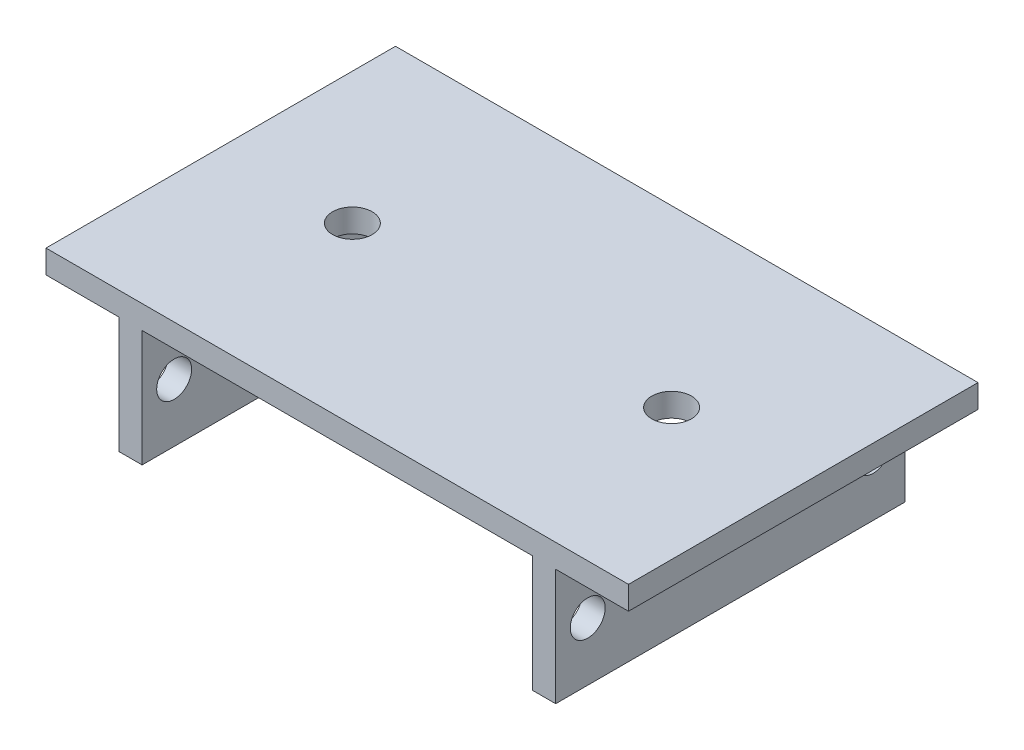
SolidWorks part; units mm, degrees
ref_plane "Front Plane" through (0, 0, 0) normal (0, 0, 1) x (1, 0, 0)
ref_plane "Top Plane" through (0, 0, 0) normal (0, 1, 0) x (1, 0, 0)
ref_plane "Right Plane" through (0, 0, 0) normal (1, 0, 0) x (0, 0, -1)
sketch "Sketch1" plane through (0, 0, 0) normal (0, 1, 0) x (1, 0, 0)
  line L1 (-72.1861, 30.4945) -> (-22.1861, 30.4945)
  line L2 (-72.1861, 30.4945) -> (-72.1861, 0.4945)
  line L3 (-72.1861, 0.4945) -> (-22.1861, 0.4945)
  line L4 (-22.1861, 30.4945) -> (-22.1861, 0.4945)
  dimension "D1" = 50
  dimension "D2" = 30
extrude "Boss-Extrude1" add sketch "Sketch1" along normal blind 2
sketch "Sketch6" plane through (0, 0, 0) normal (0, 1, 0) x (1, 0, 0)
  line L0 (-72.1861, 0.4945) -> (-22.1861, 0.4945) construction
  line L1 (-65.9361, 0.4945) -> (-63.9361, 0.4945)
  line L2 (-65.9361, 0.4945) -> (-65.9361, 30.4945)
  line L3 (-65.9361, 30.4945) -> (-63.9361, 30.4945)
  line L4 (-63.9361, 0.4945) -> (-63.9361, 30.4945)
  line L5 (-22.1861, 30.4945) -> (-72.1861, 30.4945) construction
  line L7 (-28.4361, 0.4945) -> (-30.4361, 0.4945)
  line L8 (-28.4361, 0.4945) -> (-28.4361, 30.4945)
  line L9 (-28.4361, 30.4945) -> (-30.4361, 30.4945)
  line L10 (-30.4361, 0.4945) -> (-30.4361, 30.4945)
  line L11 (-47.1861, 30.4945) -> (-47.1861, 0.4945) construction
  line L12 (-22.1861, 30.4945) -> (-72.1861, 30.4945) construction
  line L13 (-72.1861, 0.4945) -> (-22.1861, 0.4945) construction
  dimension "D1" = 33.5
  dimension "D3" = 2
extrude "Boss-Extrude2" add sketch "Sketch6" against normal blind 10
hole_wizard "M3x0.5 Tapped Hole1" positions "3DSketch2" profile "Sketch11" tap size "M3x0.5" standard "ANSI Metric"
sketch3d "3DSketch2"
  line L1 (-65.9361, -10, -30.4945) -> (-65.9361, -10, -0.4945) construction
  line L2 (-65.9361, -5, -27.7445) -> (-65.9361, -5, -3.2445) construction
  line L7 (-65.9361, 0, -30.4945) -> (-65.9361, 0, -0.4945) construction
  point P0 (-65.9361, -5, -27.7445)
  point P2 (-65.9361, -5, -3.2445)
  point P4 (-28.4361, -5, -27.7445)
  point P6 (-28.4361, -5, -3.2445)
  point P33 (-65.9361, -5, -15.4945)
  point P34 (-65.9361, 0, -15.4945)
  dimension "D1" = 24.5
  dimension "D2" = 5
sketch "Sketch11" plane through (-65.9361, -5, -27.7445) normal (0, 1, 0) x (0, 0, 1)
  line L0 (0, 0) -> (0, 10.7511)
  line L1 (0, 10.7511) -> (1.25, 10)
  line L2 (1.25, 10) -> (1.25, 6)
  line L3 (1.25, 6) -> (1.5, 6)
  line L4 (1.5, 6) -> (1.5, 0)
  line L5 (1.5, 0) -> (0, 0)
  line L10 (0, 10.7511) -> (-1.25, 10) construction
  line L11 (0, -6.35) -> (0, 107.95) construction
  dimension "Tap Drill Dia." = 2.5
  dimension "Tap Drill Depth" = 10
  dimension "Thread Major Dia." = 3
  dimension "Thread Depth" = 6
  dimension "Drill Angle" = 118
hole_wizard "M3 Clearance Hole4" positions "Sketch12" profile "Sketch13" hole size "M3" standard "ANSI Metric" end condition through all
sketch "Sketch12" plane through (0, 0, 0) normal (0, -1, 0) x (-1, 0, 0)
  line L0 (63.9361, 0.4945) -> (30.4361, 0.4945) construction
  line L1 (47.1861, 30.4945) -> (47.1861, 0.4945) construction
  line L2 (30.4361, 30.4945) -> (63.9361, 30.4945) construction
  point P0 (33.4861, 15.4945)
  point P15 (60.8861, 15.4945)
  point P16 (47.1861, 15.4945)
  dimension "D2" = 13.7
sketch "Sketch13" plane through (-33.4861, 0, -15.4945) normal (1, 0, 0) x (0, 0, -1)
  line L0 (0, 0) -> (0, 2)
  line L1 (0, 2) -> (1.7, 2)
  line L2 (1.7, 2) -> (1.7, 0)
  line L5 (1.7, 0) -> (0, 0)
  line L11 (0, -6.35) -> (0, 107.95) construction
  dimension "Thru Hole Dia." = 3.4
  dimension "Thru Hole Depth" = 2
